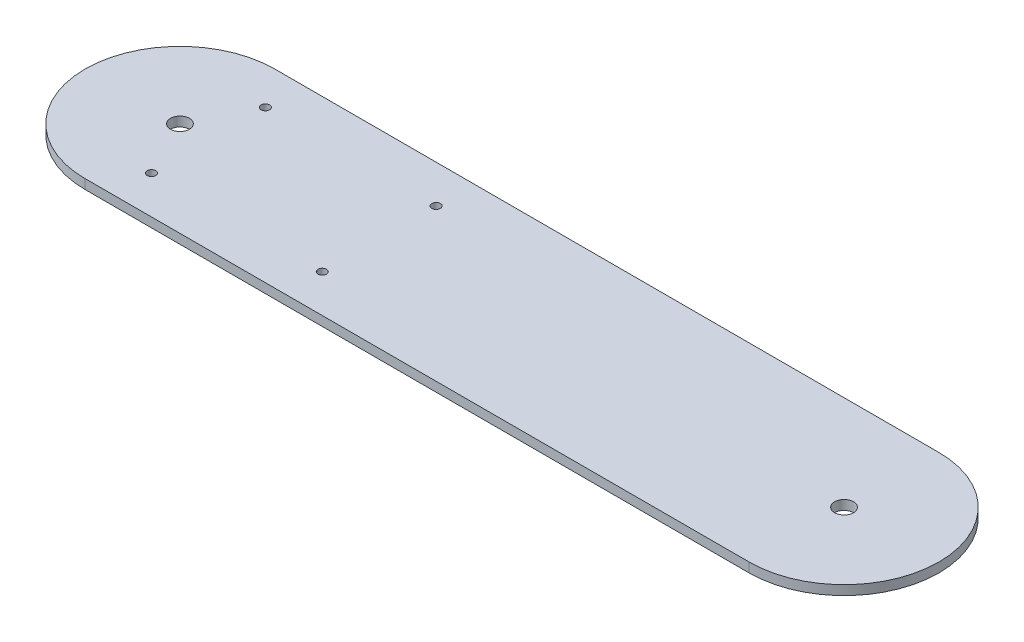
SolidWorks part; units mm, degrees
ref_plane "Front Plane" through (0, 0, 0) normal (0, 0, 1) x (1, 0, 0)
ref_plane "Top Plane" through (0, 0, 0) normal (0, 1, 0) x (1, 0, 0)
ref_plane "Right Plane" through (0, 0, 0) normal (1, 0, 0) x (0, 0, -1)
sketch "Sketch1" plane through (0, 0, 0) normal (0, 1, 0) x (1, 0, 0)
  line L0 (0, 0) -> (350, 0) construction
  line L1 (0, 50) -> (350, 50)
  line L2 (0, -50) -> (350, -50)
  circle A0 centre (0, 0) radius 5
  arc A1 (0, 50) -> (0, -50) centre (0, 0) ccw
  arc A2 (350, -50) -> (350, 50) centre (350, 0) ccw
  circle A3 centre (350, 0) radius 5
  dimension "D1" = 10
  dimension "D2" = 100
  dimension "D4" = 100
  dimension "D5" = 10
  dimension "D3" = 350
extrude "Boss-Extrude1" add sketch "Sketch1" along normal blind 5
sketch "Sketch2" plane through (0, 5, 0) normal (0, 1, 0) x (1, 0, 0)
  line L0 (15, 0) -> (0, 0) construction
  line L1 (15, 30) -> (105, 30) construction
  line L2 (15, 30) -> (15, -30) construction
  line L3 (15, -30) -> (105, -30) construction
  line L4 (105, 30) -> (105, -30) construction
  line L5 (15, 30) -> (105, -30) construction
  line L11 (25, -35) -> (95, 35) construction
  line L12 (25, 35) -> (95, -35) construction
  circle A2 centre (15, -30) radius 2.25
  circle A3 centre (105, -30) radius 2.25
  circle A4 centre (105, 30) radius 2.25
  circle A5 centre (15, 30) radius 2.25
  point P1 (60, 0)
  dimension "D4" = 2
  dimension "D6" = 70
  dimension "D1" = 60
  dimension "D2" = 90
  dimension "D3" = 15
  dimension "D7" = 70
  dimension "D5" = 2
extrude "Cut-Extrude1" cut sketch "Sketch2" against normal blind 5
sketch "Sketch3" [suppressed] plane through (0, 5, 0) normal (0, 1, 0) x (1, 0, 0)
  line L0 (15, 30) -> (105, -30) construction
  line L2 (25, -35) -> (95, -35)
  line L3 (25, -35) -> (25, 35)
  line L4 (25, 35) -> (95, 35)
  line L5 (95, -35) -> (95, 35)
  line L6 (25, -35) -> (95, 35) construction
  line L7 (25, 35) -> (95, -35) construction
  point P4 (60, 0)
  dimension "D1" = 70
  dimension "D2" = 70
extrude "Cut-Extrude2" [suppressed] cut sketch "Sketch3" against normal blind 20
